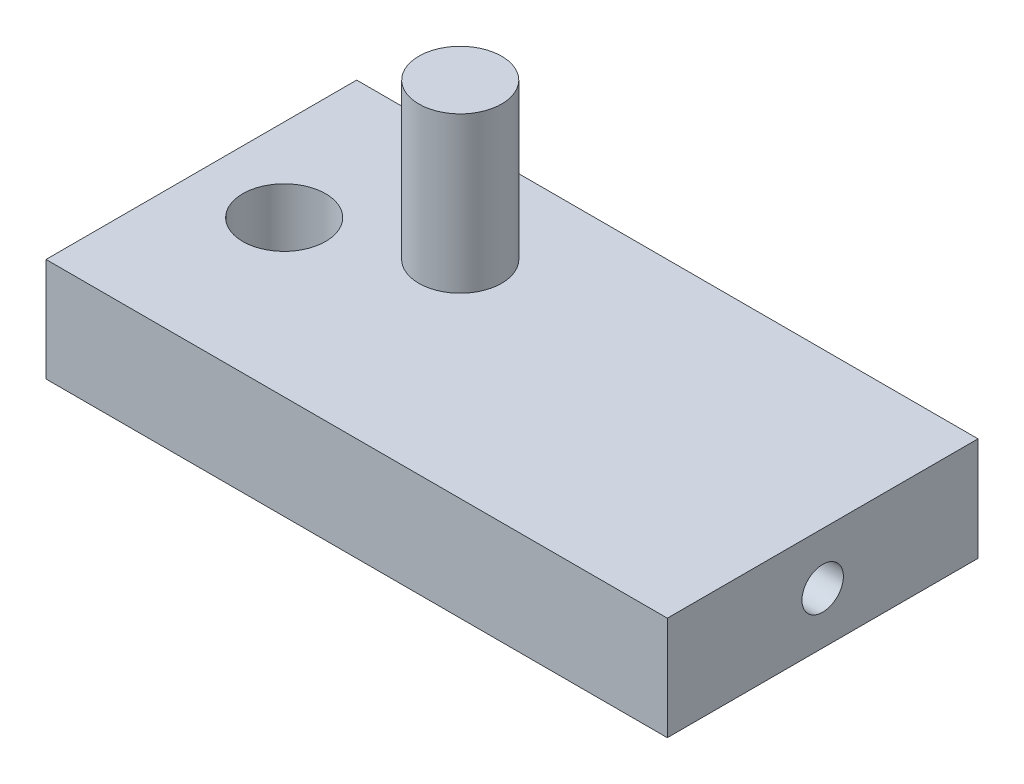
SolidWorks part; units mm, degrees
ref_plane "Front Plane" through (0, 0, 0) normal (0, 0, 1) x (1, 0, 0)
ref_plane "Top Plane" through (0, 0, 0) normal (0, 1, 0) x (1, 0, 0)
ref_plane "Right Plane" through (0, 0, 0) normal (1, 0, 0) x (0, 0, -1)
sketch "Sketch1" plane through (0, 0, 0) normal (0, 1, 0) x (1, 0, 0)
  line L1 (-15, 7.5) -> (15, 7.5)
  line L2 (-15, 7.5) -> (-15, -7.5)
  line L3 (-15, -7.5) -> (15, -7.5)
  line L4 (15, 7.5) -> (15, -7.5)
  line L5 (-15, 7.5) -> (15, -7.5) construction
  line L6 (-15, -7.5) -> (15, 7.5) construction
  circle A0 centre (-11, 0) radius 2
  circle A1 centre (-5, 2.5) radius 2
  point P0 (0, 0)
  point P10 (0, 0)
  dimension "D3" = 4
  dimension "D5" = 4
  dimension "D1" = 15
  dimension "D2" = 30
  dimension "D4" = 5
  dimension "D6" = 4
  dimension "D7" = 6
extrude "Boss-Extrude1" add sketch "Sketch1" along normal mid plane 5 contours L4 L1 L2 L3 A1 A0 region at (0.4732, 0, 0.0739)
extrude "Boss-Extrude2" add sketch "Sketch1<3>" along normal blind 10 and the other way blind 2.5 contours A1 region at (-5, 0, -2.5)
sketch "Sketch1<3>" plane through (0, 0, 0) normal (0, 1, 0) x (1, 0, 0) same geometry as "Sketch1"
sketch "Sketch2" plane through (15, 0, 0) normal (1, 0, 0) x (0, 0, -1)
  circle A0 centre (0, 0) radius 1
extrude "Cut-Extrude1" cut sketch "Sketch2" against normal blind 10
